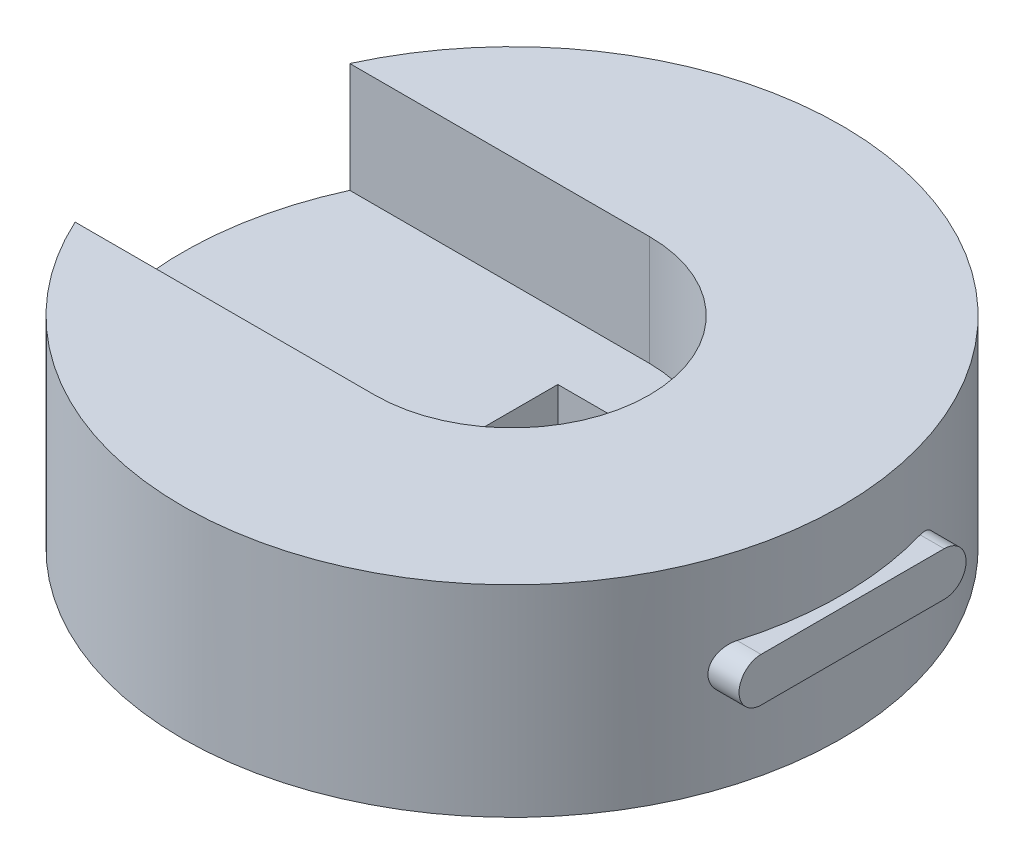
SolidWorks part; units mm, degrees
material "ABS"
ref_plane "Front Plane" through (0, 0, 0) normal (0, 0, 1) x (1, 0, 0)
ref_plane "Top Plane" through (0, 0, 0) normal (0, 1, 0) x (1, 0, 0)
ref_plane "Right Plane" through (0, 0, 0) normal (1, 0, 0) x (0, 0, -1)
sketch "Sketch2" plane through (0, 0, 0) normal (0, 1, 0) x (1, 0, 0)
  circle A0 centre (0, 0) radius 90
  dimension "D1" = 180
extrude "Boss-Extrude1" add sketch "Sketch2" along normal blind 55
sketch "Sketch3" plane through (0, 55, 0) normal (0, 1, 0) x (1, 0, 0)
  line L0 (-100.7552, 0) -> (112.8855, 0) construction
  line L1 (-144.3251, 0) -> (0, 0) construction
  line L2 (-144.3251, 37.5) -> (0, 37.5)
  line L3 (-144.3251, -37.5) -> (0, -37.5)
  arc A0 (-144.3251, 37.5) -> (-144.3251, -37.5) centre (-144.3251, 0) ccw
  arc A1 (0, -37.5) -> (0, 37.5) centre (0, 0) ccw
  point P5 (-72.1625, 0)
  dimension "D1" = 75
extrude "Cut-Extrude1" cut sketch "Sketch3" against normal blind 30
sketch "Sketch4" plane through (0, 25, 0) normal (0, 1, 0) x (1, 0, 0)
  line L1 (-7.5, 20) -> (7.5, 20)
  line L2 (-7.5, 20) -> (-7.5, -20)
  line L3 (-7.5, -20) -> (7.5, -20)
  line L4 (7.5, 20) -> (7.5, -20)
  line L5 (-7.5, 20) -> (7.5, -20) construction
  line L6 (-7.5, -20) -> (7.5, 20) construction
  point P0 (0, 0)
  dimension "D1" = 40
  dimension "D2" = 15
extrude "Cut-Extrude2" cut sketch "Sketch4" against normal through all
ref_plane "Plane2" through (50, 0, 0) normal (1, 0, 0) x (0, 0, -1)
sketch "Sketch6" plane through (50, 0, 0) normal (1, 0, 0) x (0, 0, -1)
  line L0 (-995.9617, 27.9208) -> (49004.0383, 27.9208) construction
  line L2 (0, -1000) -> (0, 49000) construction
  line L3 (-1058.4572, 55.4208) -> (48941.5428, 55.4208) construction
  line L5 (-25, 27.9208) -> (25, 27.9208) construction
  line L6 (-25, 33.9179) -> (25, 33.9179)
  line L7 (-25, 21.9238) -> (25, 21.9238)
  arc A0 (-25, 33.9179) -> (-25, 21.9238) centre (-25, 27.9208) ccw
  arc A1 (25, 21.9238) -> (25, 33.9179) centre (25, 27.9208) ccw
  point P10 (0, 27.9208)
  dimension "D1" = 27.5
  dimension "D2" = 50
curve "Curve3"
extrude "Boss-Extrude2" add sketch "Sketch6<4>" along normal blind 43
sketch "Sketch6<4>" plane through (50, 0, 0) normal (1, 0, 0) x (0, 0, -1) same geometry as "Sketch6"
